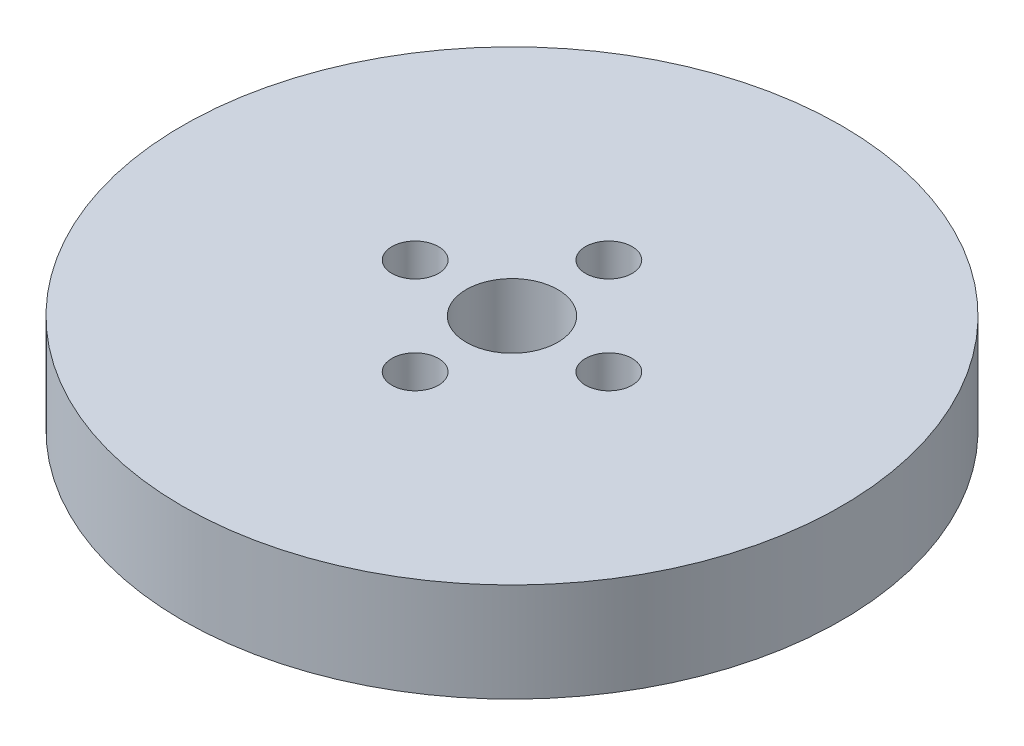
SolidWorks part; units mm, degrees
ref_plane "Front Plane" through (0, 0, 0) normal (0, 0, 1) x (1, 0, 0)
ref_plane "Top Plane" through (0, 0, 0) normal (0, 1, 0) x (1, 0, 0)
ref_plane "Right Plane" through (0, 0, 0) normal (1, 0, 0) x (0, 0, -1)
sketch "Sketch1" plane through (0, 0, 0) normal (0, 1, 0) x (1, 0, 0)
  circle A0 centre (0, 0) radius 90
  dimension "FLANGE_OD" = 180
extrude "Boss-Extrude1" add sketch "Sketch1" along normal blind 27
sketch "Sketch2" plane through (0, 0, 0) normal (0, 1, 0) x (1, 0, 0)
  circle A0 centre (0, 0) radius 12.5
  dimension "BORE_D" = 25
extrude "Cut-Extrude1" cut sketch "Sketch2" along normal through all
sketch "Sketch3" plane through (0, 27, 0) normal (0, 1, 0) x (1, 0, 0)
  circle A0 centre (0, 0) radius 26.4459 construction
  circle A1 centre (-26.4459, 0) radius 6.3627
  dimension "BOLT_D" = 12.7254
  dimension "BOLT_PCD" = 52.8917
extrude "Cut-Extrude2" cut sketch "Sketch3" against normal blind 21.9789
pattern_circular "CirPattern1" count 4 over 360 about axis through (0, 0, 0) along (0, 1, 0) of "Cut-Extrude2"
